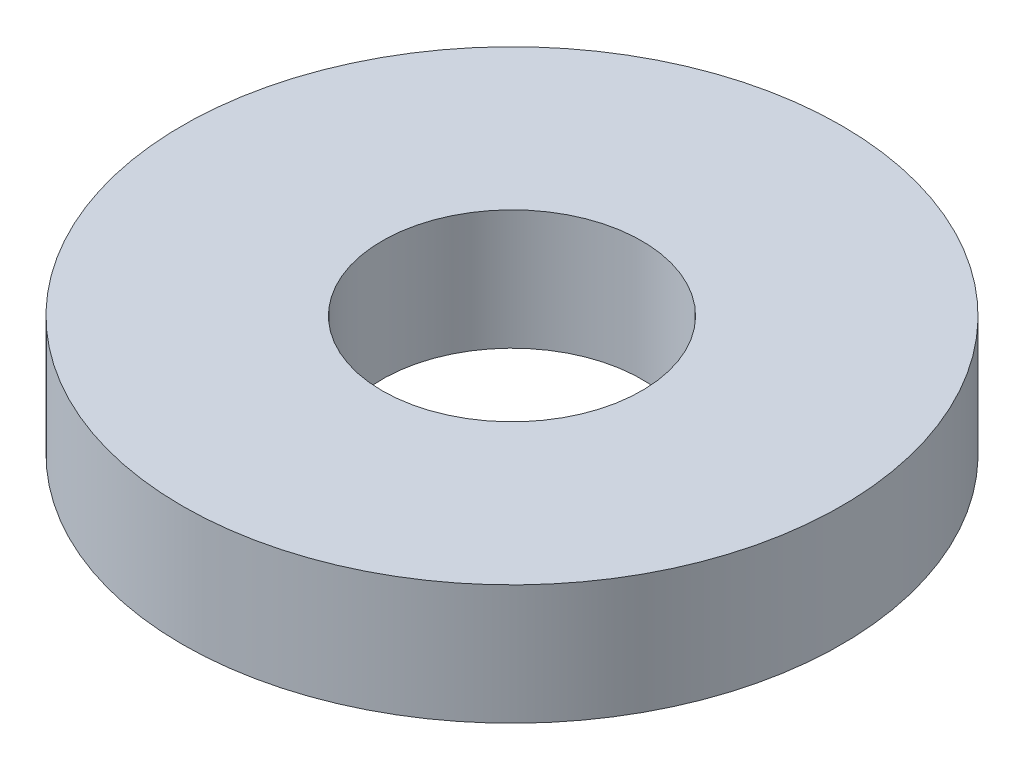
SolidWorks part; units mm, degrees
ref_plane "Front Plane" through (0, 0, 0) normal (0, 0, 1) x (1, 0, 0)
ref_plane "Top Plane" through (0, 0, 0) normal (0, 1, 0) x (1, 0, 0)
ref_plane "Right Plane" through (0, 0, 0) normal (1, 0, 0) x (0, 0, -1)
sketch "Sketch1" plane through (0, 0, 0) normal (0, 1, 0) x (1, 0, 0)
  circle A0 centre (0, 0) radius 82.5
  dimension "FLANGE_OD" = 165
extrude "Boss-Extrude1" add sketch "Sketch1" along normal blind 30
sketch "Sketch2" plane through (0, 0, 0) normal (0, 1, 0) x (1, 0, 0)
  circle A0 centre (0, 0) radius 32.5
  dimension "BORE_D" = 65
extrude "Cut-Extrude1" cut sketch "Sketch2" along normal through all
sketch "Sketch3" plane through (0, 30, 0) normal (0, 1, 0) x (1, 0, 0)
  circle A0 centre (0, 0) radius 19.4487 construction
  circle A1 centre (-19.4487, 0) radius 4.4237
  dimension "BOLT_D" = 8.8475
  dimension "BOLT_PCD" = 38.8974
extrude "Cut-Extrude2" cut sketch "Sketch3" against normal blind 20.0893 rebuild error yes
pattern_circular "CirPattern1" count 4 over 360 rebuild error yes
